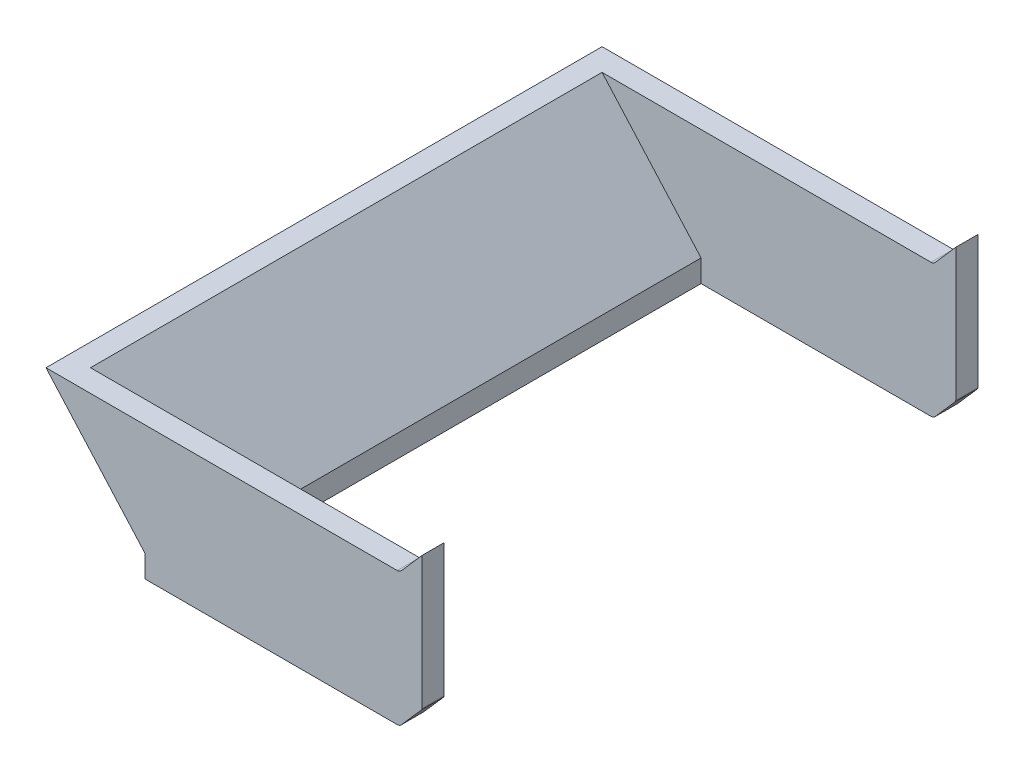
SolidWorks part; units mm, degrees
ref_plane "Front Plane" through (0, 0, 0) normal (0, 0, 1) x (1, 0, 0)
ref_plane "Top Plane" through (0, 0, 0) normal (0, 1, 0) x (1, 0, 0)
ref_plane "Right Plane" through (0, 0, 0) normal (1, 0, 0) x (0, 0, -1)
sketch "Sketch1" plane through (0, 0, 0) normal (0, 0, 1) x (1, 0, 0)
  line L0 (-0.2265, 0) -> (-22.9, 0)
  line L2 (-22.9, 2) -> (-1.7976, 2)
  line L3 (0.1494, 0.1703) -> (1.9504, 2.2238)
  line L4 (2, 2.3556) -> (2, 4)
  line L5 (-22.9, 2) -> (-22.9, 0)
  line L7 (2, 4) -> (0, 4)
  line L9 (0, 4) -> (0, 3.7417)
  arc A0 (-1.7976, 2) -> (-1.3707, 2.2396) centre (-1.7976, 2.5) ccw
  arc A1 (1.9504, 2.2238) -> (2, 2.3556) centre (1.8, 2.3556) ccw
  arc A2 (0, 3.7417) -> (-0.0889, 3.5754) centre (-0.2, 3.7417) cw
  arc A3 (0.1494, 0.1703) -> (-0.2265, 0) centre (-0.2265, 0.5) cw
  arc A6 (-0.0889, 3.5754) -> (-1.3707, 2.2396) centre (2.3, 0) ccw
  point P17 (0, 0)
  dimension "D3" = 0.2
  dimension "D1" = 0.5
  dimension "D2" = 0.2
  dimension "D4" = 0.5
extrude "Boss-Extrude1" add sketch "Sketch1" against normal blind 50
ref_plane "Plane1" through (0, 12, 0) normal (0, 1, 0) x (-1, 0, 0)
sketch "Sketch3" plane through (0, 2, 0) normal (0, 1, 0) x (1, 0, 0)
  line L1 (2, 50) -> (-22.9, 50)
  line L2 (-22.9, 50) -> (-22.9, 0)
  line L3 (2, 0) -> (-22.9, 0)
  line L7 (-20.9, 48) -> (-20.9, 2)
  line L22 (2, 0) -> (2, 2)
  line L24 (2, 48) -> (2, 50)
  line L25 (-20.9, 2) -> (2, 2)
  line L27 (-20.9, 48) -> (2, 48)
sketch "Sketch4" plane through (0, 12, 0) normal (0, 1, 0) x (-1, 0, 0)
  line L3 (-2, -50) -> (31.8, -50)
  line L4 (-2, -48) -> (29.8, -48)
  line L5 (-2, 0) -> (31.8, 0)
  line L6 (31.8, -50) -> (31.8, 0)
  line L7 (29.8, -48) -> (29.8, -2)
  line L8 (-2, -2) -> (29.8, -2)
  line L9 (-2, -50) -> (-2, -48)
  line L10 (-2, -2) -> (-2, 0)
  dimension "D1" = 2
loft "Loft1" add profiles "Sketch3", "Sketch4" connector at (-22.9, 2, -50) connector at (-31.8, 12, -50)
sketch "Sketch5" plane through (0, 0, 0) normal (0.7518, -0.6594, 0) x (0, 0, -1)
  line L0 (50, 0.2265) -> (0, 0.2265) construction
  line L1 (50, 0.2265) -> (0, 0.2265)
  line L2 (50, 0.2265) -> (51.4265, 0.2265)
  line L3 (51.4265, 0.2265) -> (51.4265, 4.4684)
  line L4 (51.4265, 4.4684) -> (-3.4334, 4.4684)
  line L5 (-3.4334, 4.4684) -> (-3.4334, 0.2265)
  line L6 (-3.4334, 0.2265) -> (0, 0.2265)
extrude "Cut-Extrude1" cut sketch "Sketch5" along normal blind 13
fillet "Fillet1" radius 0.2 2 edges at (2, 2.2804, -49) (2, 2.2804, -1)
sketch "Sketch6" plane through (2, 0, 0) normal (1, 0, 0) x (0, 0, -1)
  line L0 (2, 4) -> (2, 12) construction
  line L1 (48, 4) -> (48, 12) construction
  line L2 (2, 4) -> (2, 12)
  line L3 (48, 4) -> (48, 12)
  line L4 (2, 4) -> (2, -3.39)
  line L5 (2, -3.39) -> (48, -3.39)
  line L6 (48, -3.39) -> (48, 4)
  line L7 (48, 12) -> (2, 12)
extrude "Cut-Extrude2" cut sketch "Sketch6" against normal up to vertex (22.9 mm away) up to point (-20.9, 2, -48)
sketch "Sketch7" plane through (0, 0, 0) normal (0, 0, 1) x (1, 0, 0)
  line L0 (2, 14.2804) -> (2, 12)
  line L1 (2, 12) -> (-0.2265, 12)
  line L3 (0.1494, 12.1703) -> (2, 14.2804)
  arc A2 (-0.2265, 12) -> (0.1494, 12.1703) centre (-0.2265, 12.5) ccw
extrude "Boss-Extrude2" add sketch "Sketch7" against normal up to surface (2 mm away)
extrude "Boss-Extrude4" add sketch "Sketch7<2>" against normal up to surface (50 mm away) from vertex up to face at (-6.4059, 2.482, -50) starting at point (2, 12, -48)
sketch "Sketch7<2>" plane through (0, 0, 0) normal (0, 0, 1) x (1, 0, 0) same geometry as "Sketch7"
